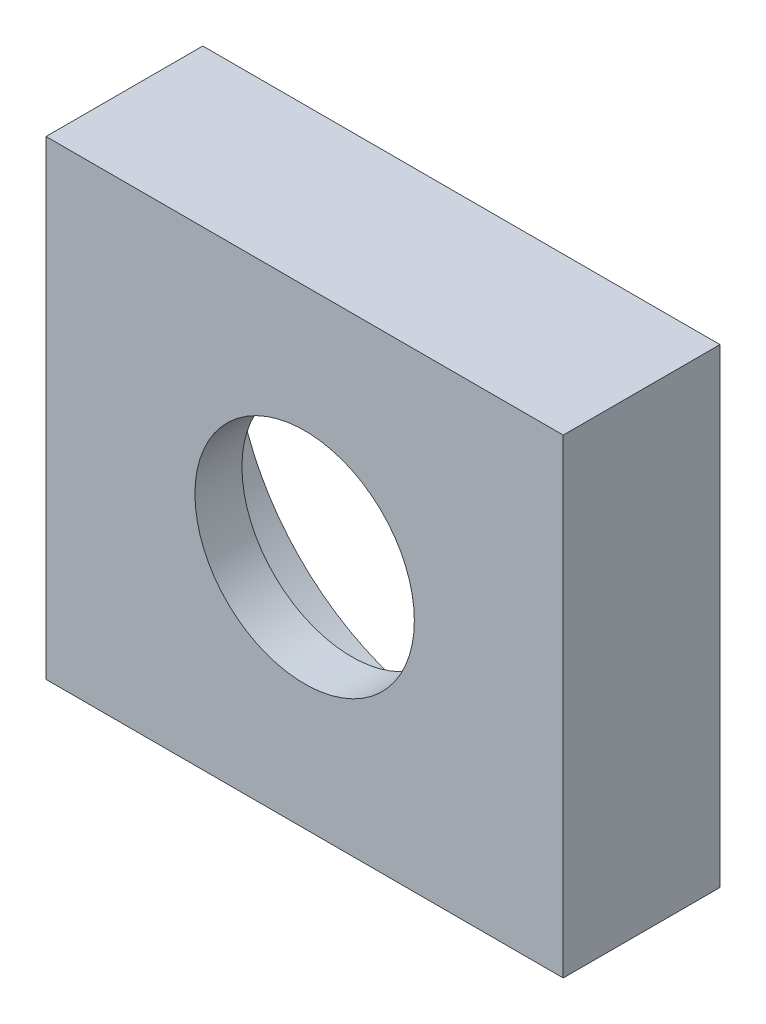
SolidWorks part; units mm, degrees
material "1060 Alloy"
ref_plane "Front Plane" through (0, 0, 0) normal (0, 0, 1) x (1, 0, 0)
ref_plane "Top Plane" through (0, 0, 0) normal (0, 1, 0) x (1, 0, 0)
ref_plane "Right Plane" through (0, 0, 0) normal (1, 0, 0) x (0, 0, -1)
sketch "Sketch1" plane through (0, 0, 0) normal (0, 0, 1) x (1, 0, 0)
  line L1 (0, 0) -> (33, 0)
  line L2 (0, 0) -> (0, 30)
  line L3 (0, 30) -> (33, 30)
  line L4 (33, 0) -> (33, 30)
  dimension "D1" = 30
  dimension "D2" = 33
extrude "Boss-Extrude1" add sketch "Sketch1" along normal blind 10
sketch "Sketch2" plane through (0, 0, 10) normal (0, 0, 1) x (1, 0, 0)
  line L0 (0, 30) -> (0, 0) construction
  line L1 (0, 0) -> (33, 0) construction
  circle A0 centre (16.5, 15) radius 7
  dimension "D1" = 14
  dimension "D2" = 16.5
  dimension "D3" = 15
extrude "Cut-Extrude1" cut sketch "Sketch2" against normal up to next
sketch "Sketch3" plane through (0, 0, 0) normal (0, 0, -1) x (-1, 0, 0)
  circle A0 centre (-16.5, 15) radius 14.5
  dimension "D1" = 29
extrude "Cut-Extrude2" cut sketch "Sketch3" against normal offset from surface (7 mm away) 3 up to face at (23.5, 15, 10)
hole_wizard "Tap Drill for M3 Tap1" positions "Sketch5" profile "Sketch4" hole size "M3" standard "ISO"
sketch "Sketch5" plane through (0, 0, 0) normal (0, -1, 0) x (-1, 0, 0)
  line L0 (0, -10) -> (-33, -10) construction
  line L1 (-33, -10) -> (-33, 0) construction
  line L2 (0, -10) -> (0, 0) construction
  point P0 (-3, -6)
  point P2 (-30, -6)
  dimension "D1" = 4
  dimension "D2" = 3
  dimension "D3" = 3
sketch "Sketch4" plane through (3, 0, 6) normal (1, 0, 0) x (0, 0, -1)
  line L0 (0, 0) -> (0, 8.7511)
  line L1 (0, 8.7511) -> (1.25, 8)
  line L2 (1.25, 8) -> (1.25, 0)
  line L5 (1.25, 0) -> (0, 0)
  line L10 (0, 8.7511) -> (-1.25, 8) construction
  line L11 (0, -6.35) -> (0, 107.95) construction
  dimension "Hole Dia." = 2.5
  dimension "Hole Depth" = 8
  dimension "Drill Angle" = 118
